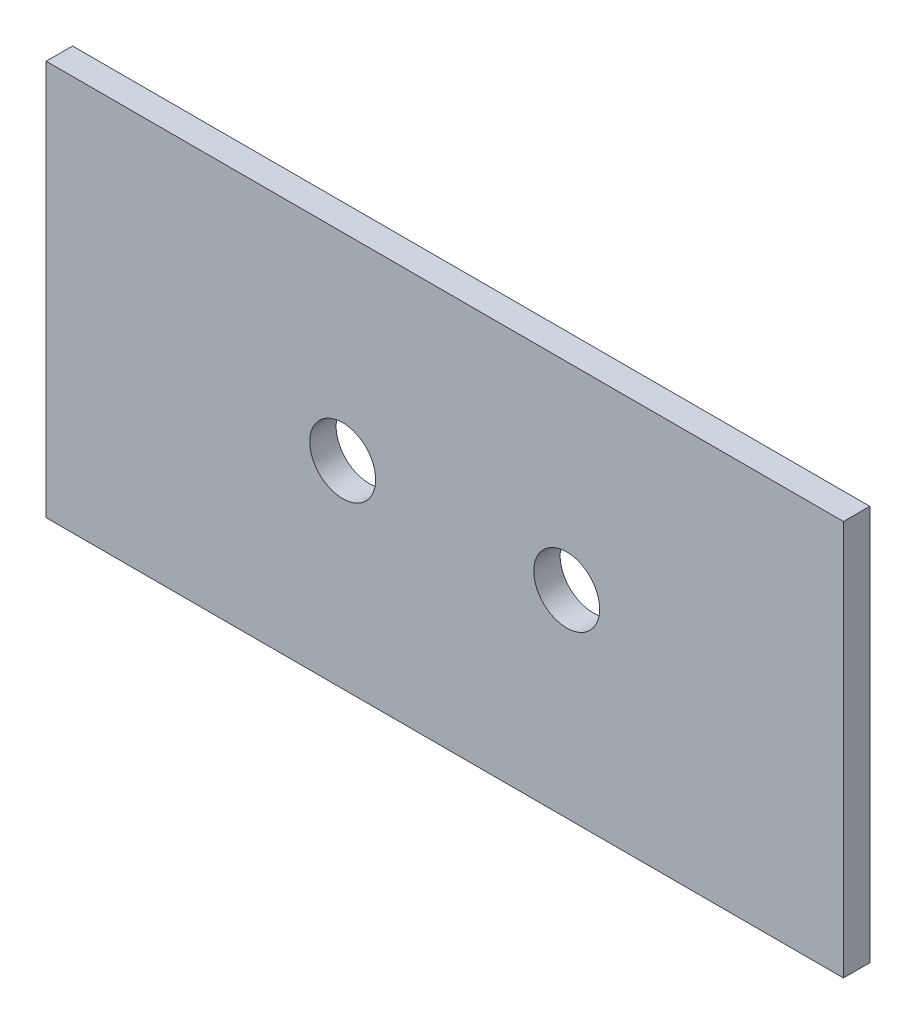
SolidWorks part; units mm, degrees
ref_plane "Front Plane" through (0, 0, 0) normal (0, 0, 1) x (1, 0, 0)
ref_plane "Top Plane" through (0, 0, 0) normal (0, 1, 0) x (1, 0, 0)
ref_plane "Right Plane" through (0, 0, 0) normal (1, 0, 0) x (0, 0, -1)
sketch "Sketch1" plane through (0, 0, 0) normal (0, 0, 1) x (1, 0, 0)
  line L1 (-79, -20) -> (42, -20)
  line L2 (-79, -20) -> (-79, 40)
  line L3 (-79, 40) -> (42, 40)
  line L4 (42, -20) -> (42, 40)
  circle A2 centre (-34, 10) radius 5
  circle A3 centre (0, 10) radius 5
  point P1 (0, 0)
  point P6 (-79, 10)
  point P7 (42, 10)
  dimension "D3" = 0
  dimension "D4" = 121
  dimension "D5" = 45
  dimension "D7" = 34
  dimension "D10" = 10
  dimension "D2" = 60
extrude "Boss-Extrude1" add sketch "Sketch1" along normal blind 4
